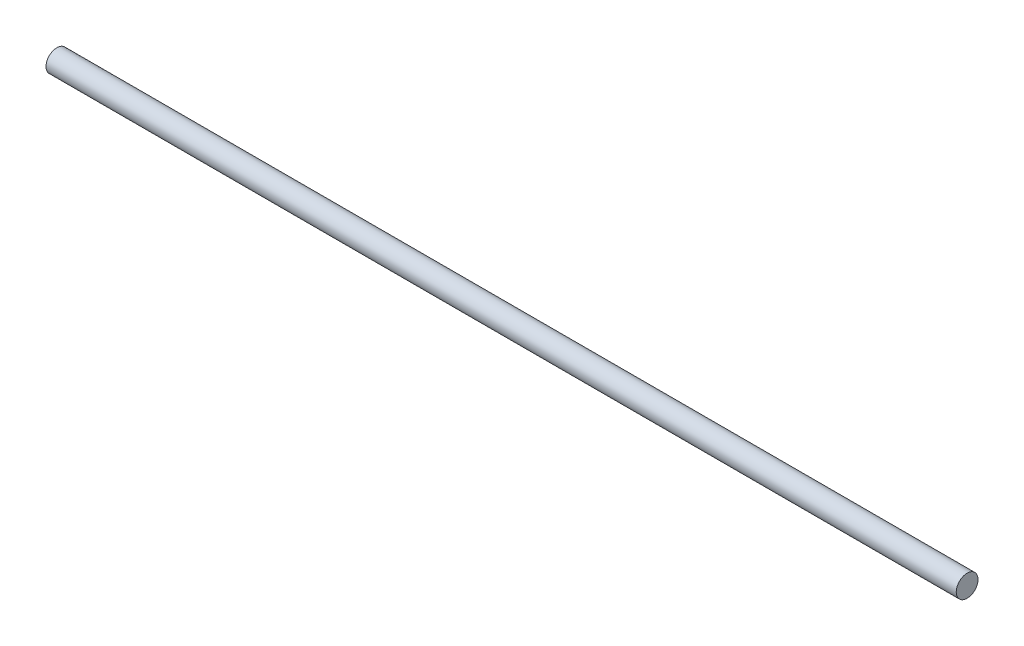
SolidWorks part; units mm, degrees
ref_plane "Front Plane" through (0, 0, 0) normal (0, 0, 1) x (1, 0, 0)
ref_plane "Top Plane" through (0, 0, 0) normal (0, 1, 0) x (1, 0, 0)
ref_plane "Right Plane" through (0, 0, 0) normal (1, 0, 0) x (0, 0, -1)
sketch "Sketch1" plane through (0, 0, 0) normal (1, 0, 0) x (0, 0, -1)
  circle A0 centre (0, 0) radius 4
  dimension "D1" = 8
extrude "Boss-Extrude1" add sketch "Sketch1" along normal blind 334
